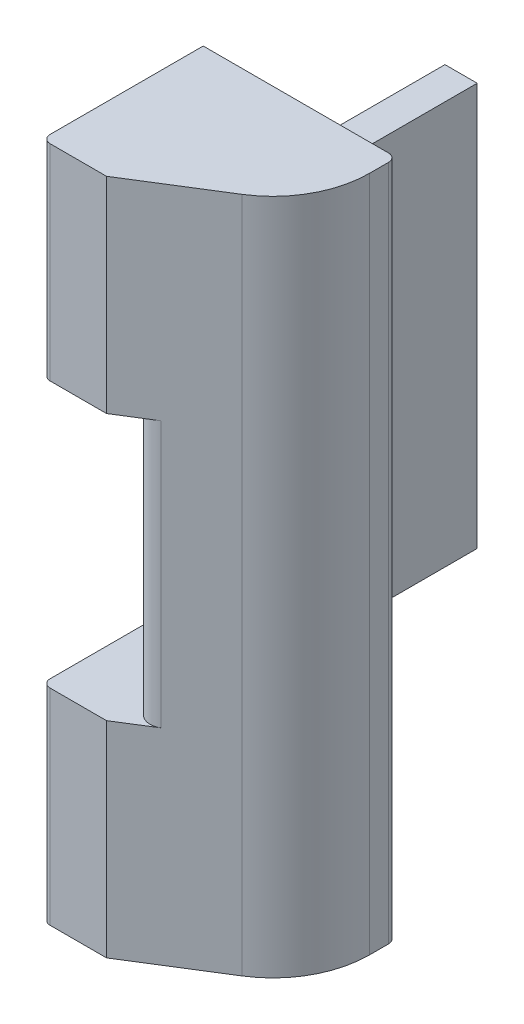
SolidWorks part; units mm, degrees
ref_plane "Front Plane" through (0, 0, 0) normal (0, 0, 1) x (1, 0, 0)
ref_plane "Top Plane" through (0, 0, 0) normal (0, 1, 0) x (1, 0, 0)
ref_plane "Right Plane" through (0, 0, 0) normal (1, 0, 0) x (0, 0, -1)
sketch "Sketch1" plane through (0, 0, 0) normal (0, 0, 1) x (1, 0, 0)
  line L0 (0, 21) -> (0, 8.25) construction
  line L1 (-6, -21) -> (6, -21)
  line L2 (-6, -21) -> (-6, -8.25)
  line L3 (-6, 21) -> (6, 21)
  line L4 (6, -21) -> (6, 21)
  line L5 (-2, -8.25) -> (-2, 8.25)
  line L6 (-2, 8.25) -> (-6, 8.25)
  line L7 (0, -21) -> (0, -8.25) construction
  line L8 (-6, -8.25) -> (-2, -8.25)
  line L9 (-6, 8.25) -> (-6, 21)
  point P0 (0, 0)
extrude "Boss-Extrude1" add sketch "Sketch1" along normal blind 10
sketch "Sketch2" plane through (0, 0, 0) normal (0, 1, 0) x (1, 0, 0)
  line L0 (-6, -10) -> (-2, -10) construction
  line L1 (6, -10) -> (-6, -10) construction
  line L2 (-2, -10) -> (6, -5)
  line L3 (6, -10) -> (6, 0) construction
  line L4 (6, -5) -> (6, -10)
  line L5 (6, -10) -> (-2, -10)
extrude "Cut-Extrude1" cut sketch "Sketch2" against normal blind 30 and the other way blind 30
sketch "Sketch8" plane through (0, 0, 0) normal (0, 1, 0) x (1, 0, 0)
  line L0 (-2, -10) -> (-2, -9) construction
  line L1 (-2, 0) -> (-2, -9)
  line L2 (6, -5) -> (6, -4.4661) construction
  line L3 (6, -5) -> (6, 0) construction
  line L4 (6, -4.4661) -> (5, -4.4661) construction
  line L5 (-2, -9) -> (5, -4.4661)
  line L6 (5, -4.4661) -> (5, 0)
  line L7 (6, 0) -> (-6, 0) construction
  line L8 (5, 0) -> (-2, 0)
extrude "Cut-Extrude4" cut sketch "Sketch8" against normal blind 8.25 and the other way blind 8.25
fillet "Fillet3" radius 0.5 3 edges at (-6, -14.625, 10) (-6, 14.625, 10) (6, 0, 0)
sketch "Sketch4" plane through (0, 0, 0) normal (1, 0, 0) x (0, 0, -1)
  line L0 (0, 0) -> (5, 0) construction
  line L5 (0, -21) -> (0, 21) construction
  line L6 (15, -12.5) -> (0, -12.5)
  line L7 (15, -12.5) -> (15, 12.5)
  line L8 (15, 12.5) -> (0, 12.5)
  line L9 (0, -12.5) -> (0, 12.5)
extrude "Boss-Extrude2" add sketch "Sketch4" along normal blind 2 from surface at -6 starting at face at (-6, -14.625, 4.75)
fillet "Fillet5" radius 6 2 edges at (-4, 10.375, 0) (-4, -10.375, 0)
fillet "Fillet10" radius 2 2 edges at (-2, 12.5, 0) (-2, -12.5, 0)
fillet "Fillet19" radius 6 1 edges at (6, 0, 5)
sketch "Sketch9" plane through (0, 0, 0) normal (0, 0, 1) x (1, 0, 0)
  line L0 (-2, 8.25) -> (-2, -8.25) construction
  line L1 (-2.5568, -8.25) -> (-1.4432, -8.25)
  line L2 (-2.5568, -8.25) -> (-2.5568, 8.25)
  line L3 (-2.5568, 8.25) -> (-1.4432, 8.25)
  line L4 (-1.4432, -8.25) -> (-1.4432, 8.25)
  line L5 (-2.5568, -8.25) -> (-1.4432, 8.25) construction
  line L6 (-2.5568, 8.25) -> (-1.4432, -8.25) construction
  point P0 (-2, 0)
extrude "Cut-Extrude5" cut sketch "Sketch9" along normal blind 10
fillet "Fillet21" radius 1 4 edges at (5, 0, 0) (5, 0, 4.4661) (-1.4432, 0, 8.6393) (-1.4432, 0, 9.652)
